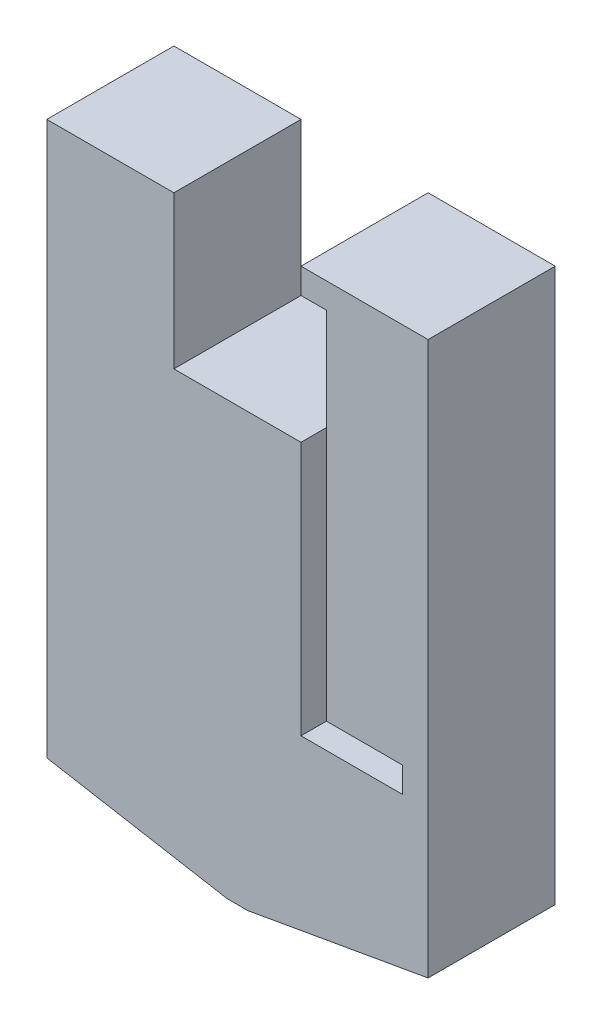
SolidWorks part; units mm, degrees
material "6061 Alloy"
ref_plane "Front Plane" through (0, 0, 0) normal (0, 0, 1) x (1, 0, 0)
ref_plane "Top Plane" through (0, 0, 0) normal (0, 1, 0) x (1, 0, 0)
ref_plane "Right Plane" through (0, 0, 0) normal (1, 0, 0) x (0, 0, -1)
sketch "Sketch2" plane through (0, 0, 0) normal (0, 0, 1) x (1, 0, 0)
  line L1 (-9.525, -15.875) -> (9.525, -15.875)
  line L2 (-9.525, -15.875) -> (-9.525, 15.875)
  line L3 (-9.525, 15.875) -> (9.525, 15.875)
  line L4 (9.525, -15.875) -> (9.525, 15.875)
  line L5 (-9.525, -15.875) -> (9.525, 15.875) construction
  line L6 (-9.525, 15.875) -> (9.525, -15.875) construction
  point P0 (0, 0)
  dimension "D1" = 31.75
  dimension "D2" = 19.05
extrude "Boss-Extrude1" add sketch "Sketch2" along normal mid plane 6.35
sketch "Sketch4" plane through (-1.5069, 3.1105, 3.175) normal (0, 0, 1) x (1, 0, 0)
  line L1 (-1.6681, 12.7645) -> (4.6819, 12.7645)
  line L2 (-1.6681, 12.7645) -> (-1.6681, 2.6045)
  line L3 (-1.6681, 2.6045) -> (4.6819, 2.6045)
  line L4 (4.6819, 12.7645) -> (4.6819, 2.6045)
  line L7 (-8.0181, 12.7645) -> (11.0319, 12.7645)
  line L8 (-8.0181, 12.7645) -> (-8.0181, 10.2245)
  line L9 (-8.0181, 10.2245) -> (11.0319, 10.2245)
  line L10 (11.0319, 12.7645) -> (11.0319, 10.2245)
  line L11 (11.0319, 12.7645) -> (-8.0181, 12.7645) construction
  line L12 (11.0319, -18.9855) -> (11.0319, 12.7645) construction
  line L13 (-8.0181, 12.7645) -> (-8.0181, -18.9855) construction
  dimension "D1" = 6.35
  dimension "D2" = 0
  dimension "D3" = 10.16
  dimension "D4" = 2.54
  dimension "D5" = 0
  dimension "D6" = 0
  dimension "D7" = 0
  dimension "D8" = 6.35
extrude "Cut-Extrude1" cut sketch "Sketch4" against normal through all contours L4 L9 | L2 L9 L4 | L9 L2 L3 L4 | L9 L2 region at (0, 14.605, 3.175) region at (-6.35, 14.605, 3.175) region at (6.35, 14.605, 3.175) region at (0, 9.525, 3.175)
sketch "Sketch6" plane through (-1.5069, 3.1105, 3.175) normal (0, 0, 1) x (1, 0, 0)
  line L0 (4.6819, 10.2245) -> (4.6819, 2.6045) construction
  line L5 (4.6819, 8.9545) -> (5.9519, 8.9545)
  line L6 (4.6819, 8.9545) -> (4.6819, -10.0955)
  line L7 (4.6819, -10.0955) -> (5.9519, -10.0955)
  line L8 (5.9519, 8.9545) -> (5.9519, -10.0955)
  line L12 (4.6819, -10.0955) -> (9.7619, -10.0955)
  line L13 (4.6819, -10.0955) -> (4.6819, -8.8255)
  line L14 (4.6819, -8.8255) -> (9.7619, -8.8255)
  line L15 (9.7619, -10.0955) -> (9.7619, -8.8255)
  line L16 (4.6819, 10.2245) -> (11.0319, 10.2245) construction
  line L17 (-8.0181, -18.9855) -> (11.0319, -18.9855) construction
  line L18 (11.0319, -18.9855) -> (11.0319, 10.2245) construction
  point P7 (5.3169, -10.0955)
  dimension "D1" = 1.27
  dimension "D2" = 1.27
  dimension "D3" = 8.89
  dimension "D4" = 1.27
  dimension "D5" = 1.27
extrude "Cut-Extrude2" cut sketch "Sketch6" against normal through all contours L6 L14 L8 L5 | L14 L6 L7 L8 | L12 L15 L14 L8 region at (3.81, 3.175, 3.175) region at (3.81, -6.35, 3.175) region at (6.35, -6.35, 3.175)
sketch "Sketch7" plane through (0, 0, 3.175) normal (0, 0, 1) x (1, 0, 0)
  line L0 (-9.525, -14.2875) -> (-0.5218, -15.875)
  line L1 (-9.525, 13.335) -> (-9.525, -15.875) construction
  line L2 (-9.525, -15.875) -> (9.525, -15.875) construction
  line L3 (-0.5218, -15.875) -> (-9.525, -15.875)
  line L4 (-9.525, -15.875) -> (-9.525, -14.2875)
  dimension "D1" = 1.5875
  dimension "D2" = 80
extrude "Cut-Extrude3" cut sketch "Sketch7" against normal through all
mirror "Mirror1" about plane through (0, 0, 0) normal (1, 0, 0) of "Cut-Extrude3"
